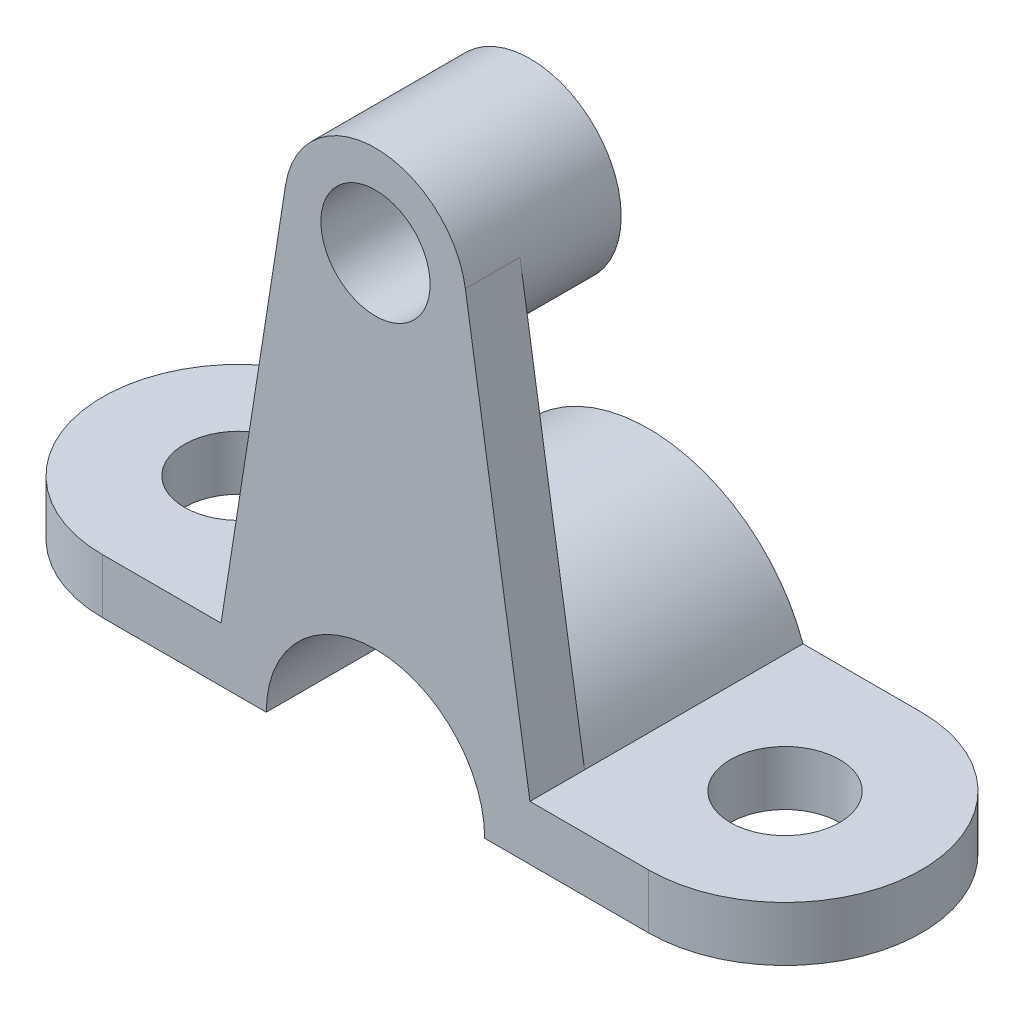
SolidWorks part; units mm, degrees
ref_plane "Front Plane" through (0, 0, 0) normal (0, 0, 1) x (1, 0, 0)
ref_plane "Top Plane" through (0, 0, 0) normal (0, 1, 0) x (1, 0, 0)
ref_plane "Right Plane" through (0, 0, 0) normal (1, 0, 0) x (0, 0, -1)
sketch "Sketch2" plane through (0, 0, 0) normal (0, 0, 1) x (1, 0, 0)
  line L0 (-36, 0) -> (-24, 0)
  line L1 (24, 0) -> (36, 0)
  arc A0 (36, 0) -> (-36, 0) centre (0, 0) ccw
  arc A1 (24, 0) -> (-24, 0) centre (0, 0) ccw
  dimension "D1" = 36
  dimension "D2" = 24
extrude "Boss-Extrude1" add sketch "Sketch2" along normal mid plane 60
sketch "Sketch3" plane through (0, 0, 0) normal (0, 1, 0) x (1, 0, 0)
  line L0 (36, 30) -> (60, 30)
  line L1 (60, -30) -> (36, -30)
  line L2 (36, -30) -> (30, -30)
  line L3 (-36, -30) -> (36, -30) construction
  line L4 (30, -30) -> (30, 30)
  line L5 (30, 30) -> (36, 30)
  line L6 (0, 41.9648) -> (0, -45.183) construction
  line L7 (-30, 30) -> (-36, 30)
  line L8 (-30, -30) -> (-30, 30)
  line L9 (-36, -30) -> (-30, -30)
  line L10 (-60, -30) -> (-36, -30)
  line L11 (-36, 30) -> (-60, 30)
  arc A0 (60, 30) -> (60, -30) centre (60, 0) cw
  arc A1 (-60, 30) -> (-60, -30) centre (-60, 0) ccw
  point P14 (0, 0)
  point P17 (32.7542, 28.125)
  dimension "D1" = 60
  dimension "D2" = 60
  dimension "D3" = 30
extrude "Boss-Extrude2" add sketch "Sketch3" along normal blind 12
sketch "Sketch4" plane through (0, 0, 30) normal (0, 0, 1) x (1, 0, 0)
  line L0 (0, 0) -> (0, 99.3898) construction
  line L1 (-19.7588, 102.4867) -> (-33.9411, 12)
  line L2 (19.7588, 102.4867) -> (33.9411, 12)
  circle A0 centre (0, 99.3898) radius 20
  circle A1 centre (0, 99.3898) radius 12
  arc A2 (33.9411, 12) -> (-33.9411, 12) centre (0, 0) ccw construction
  arc A3 (33.9411, 12) -> (-33.9411, 12) centre (0, 0) ccw
  point P11 (0, 0)
  point P12 (0, 0)
  arc M8 (33.9411, 12) -> (-33.9411, 12) centre (0, 0) ccw
  dimension "D1" = 24
  dimension "D2" = 40
extrude "Boss-Extrude3" add sketch "Sketch4" against normal blind 34 separate body contours A0
extrude "Cut-Extrude1" cut sketch "Sketch4<3>" against normal blind 34 contours A1
sketch "Sketch4<3>" plane through (0, 0, 30) normal (0, 0, 1) x (1, 0, 0) same geometry as "Sketch4"
extrude "Boss-Extrude4" add sketch "Sketch4<4>" against normal blind 12 contours L0 L2 A0 M8 | A3 L0 A0 L1 region at (-15.0922, 55.8895, 30) region at (15.0922, 55.8895, 30)
sketch "Sketch4<4>" plane through (0, 0, 30) normal (0, 0, 1) x (1, 0, 0) same geometry as "Sketch4"
sketch "Sketch5" plane through (0, 12, 0) normal (0, 1, 0) x (1, 0, 0)
  circle A0 centre (-60, 0) radius 12
  dimension "D1" = 24
extrude "Cut-Extrude2" cut sketch "Sketch5" against normal through all
mirror "Mirror1" about plane through (0, 0, 0) normal (1, 0, 0) of "Cut-Extrude2"
